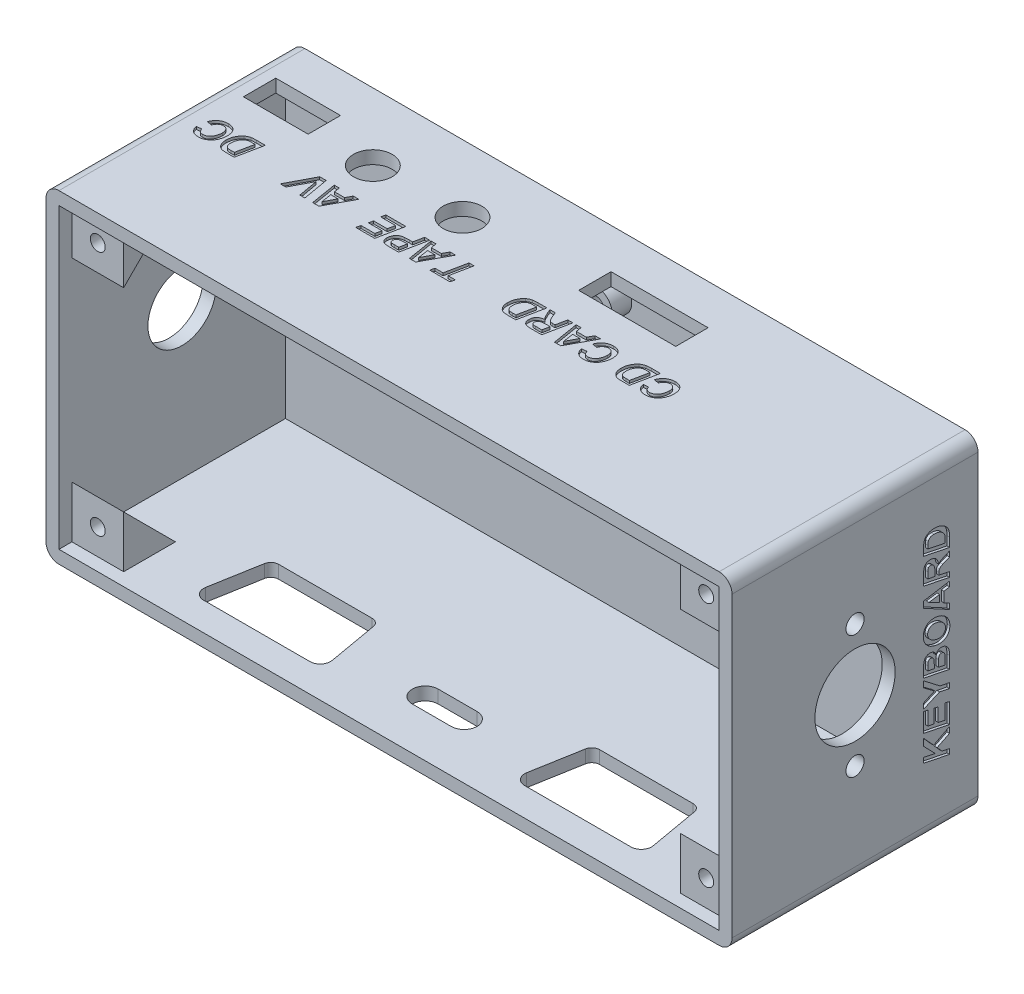
SolidWorks part; units mm, degrees
material "ABS"
ref_plane "Спереди" through (0, 0, 0) normal (0, 0, 1) x (1, 0, 0)
ref_plane "Сверху" through (0, 0, 0) normal (0, 1, 0) x (1, 0, 0)
ref_plane "Справа" through (0, 0, 0) normal (1, 0, 0) x (0, 0, -1)
sketch "Эскиз1" plane through (0, 0, 0) normal (0, 0, 1) x (1, 0, 0)
  line L1 (-53, -25) -> (53, -25)
  line L2 (-53, -25) -> (-53, 25)
  line L3 (-53, 25) -> (53, 25)
  line L4 (53, -25) -> (53, 25)
  line L5 (-53, -25) -> (53, 25) construction
  line L6 (-53, 25) -> (53, -25) construction
  point P0 (0, 0)
  dimension "D1" = 106
  dimension "D2" = 50
extrude "CaseBody" add sketch "Эскиз1" along normal blind 3
sketch "Эскиз2" plane through (0, 0, 3) normal (0, 0, 1) x (1, 0, 0)
  line L0 (53, 25) -> (-53, 25) construction
  line L1 (-51, -23) -> (51, -23)
  line L2 (-51, -23) -> (-51, 23)
  line L3 (-51, 23) -> (51, 23)
  line L4 (51, -23) -> (51, 23)
  line L5 (-51, -23) -> (51, 23) construction
  line L6 (-51, 23) -> (51, -23) construction
  line L7 (53, -25) -> (53, 25) construction
  line L9 (-53, -25) -> (53, -25)
  line L10 (-53, -25) -> (-53, 25)
  line L11 (-53, 25) -> (53, 25)
  line L12 (53, -25) -> (53, 25)
  line L13 (-53, -25) -> (53, 25) construction
  line L14 (-53, 25) -> (53, -25) construction
  point P0 (0, 0)
  point P10 (0, 0)
  dimension "D1" = 2
  dimension "D2" = 2
extrude "CaseBody2" add sketch "Эскиз2" along normal blind 35
sketch "Эскиз3" plane through (0, 0, 3) normal (0, 0, 1) x (1, 0, 0)
  line L0 (51, 23) -> (-51, 23) construction
  line L1 (-46.625, 1.53) -> (46.625, 1.53) construction
  line L2 (-46.625, 1.53) -> (-46.625, 19.18) construction
  line L3 (-46.625, 19.18) -> (46.625, 19.18) construction
  line L4 (46.625, 1.53) -> (46.625, 19.18) construction
  line L5 (-46.625, 1.53) -> (46.625, 19.18) construction
  line L6 (-46.625, 19.18) -> (46.625, 1.53) construction
  circle A0 centre (-46.625, 1.53) radius 2.5
  circle A1 centre (46.625, 1.53) radius 2.5
  circle A2 centre (0.005, 19.18) radius 2.5
  point P0 (0, 0)
  point P13 (0, 10.355)
  dimension "D4" = 5
  dimension "D1" = 93.25
  dimension "D2" = 17.65
  dimension "D3" = 46.63
  dimension "D5" = 3.82
extrude "SizifXXSFix" add sketch "Эскиз3" along normal blind 3
sketch "Эскиз4" plane through (0, 0, 6) normal (0, 0, 1) x (1, 0, 0)
  circle A0 centre (-46.625, 1.53) radius 1.2
  circle A1 centre (0.005, 19.18) radius 1.2
  circle A2 centre (46.625, 1.53) radius 1.2
  dimension "D1" = 2.4
extrude "Holes2_5" cut sketch "Эскиз4" against normal blind 5.6
sketch "Эскиз5" plane through (0, 25, 0) normal (0, 1, 0) x (1, 0, 0)
  line L1 (-49.3, -6.2) -> (-39.3, -6.2)
  line L2 (-49.3, -6.2) -> (-49.3, -11.2)
  line L3 (-49.3, -11.2) -> (-39.3, -11.2)
  line L4 (-39.3, -6.2) -> (-39.3, -11.2)
  line L5 (-49.3, -6.2) -> (-39.3, -11.2) construction
  line L6 (-49.3, -11.2) -> (-39.3, -6.2) construction
  line L7 (2.5, -6.2) -> (17.5, -6.2)
  line L8 (2.5, -6.2) -> (2.5, -11.2)
  line L9 (2.5, -11.2) -> (17.5, -11.2)
  line L10 (17.5, -6.2) -> (17.5, -11.2)
  line L11 (2.5, -6.2) -> (17.5, -11.2) construction
  line L12 (2.5, -11.2) -> (17.5, -6.2) construction
  line L13 (53, 0) -> (-53, 0) construction
  line L14 (-53, -38) -> (-53, 0) construction
  circle A0 centre (-30.1, -10.4) radius 3
  circle A1 centre (-16.25, -10.4) radius 3
  point P0 (-44.3, -8.7)
  point P9 (10, -8.7)
  dimension "D5" = 6
  dimension "D2" = 10
  dimension "D3" = 6.2
  dimension "D4" = 5
  dimension "D6" = 13.85
  dimension "D7" = 14.2
  dimension "D8" = 26.25
  dimension "D9" = 10.4
  dimension "D10" = 5
  dimension "D11" = 15
  dimension "D12" = 22.9
extrude "SizifXXS_Holes" cut sketch "Эскиз5" against normal up to next
sketch "Эскиз7" plane through (53, 0, 0) normal (1, 0, 0) x (0, 0, -1)
  line L0 (-20, 0) -> (-6.0564, 0) construction
  line L2 (0, -25) -> (0, 25) construction
  circle A0 centre (-19, 0) radius 6.2
  circle A1 centre (-19, -9.5) radius 1.4
  circle A2 centre (-19, 9.5) radius 1.4
  dimension "D1" = 12.4
  dimension "D4" = 2.8
  dimension "D2" = 19
  dimension "D3" = 19
extrude "PS2Hole" cut sketch "Эскиз7" against normal up to next
sketch "Эскиз8" plane through (51, 0, 0) normal (-1, 0, 0) x (0, 0, 1)
  line L0 (36, 23) -> (36, 15)
  line L1 (38, 23) -> (3, 23) construction
  line L2 (36, 15) -> (28, 23)
  line L3 (28, 23) -> (36, 23)
  line L4 (38, -23) -> (38, 23) construction
  dimension "D1" = 8
  dimension "D2" = 8
  dimension "D3" = 2
extrude "CaseTopFix" add sketch "Эскиз8" along normal blind 8
sketch "Эскиз9" plane through (0, 0, 36) normal (0, 0, 1) x (1, 0, 0)
  line L0 (43, 15) -> (43, 23) construction
  line L1 (43, 23) -> (51, 23) construction
  line L2 (43, 23) -> (43, 15) construction
  line L3 (43, 15) -> (51, 15) construction
  line L4 (51, 23) -> (51, 15) construction
  line L5 (43, 23) -> (51, 15) construction
  line L6 (43, 15) -> (51, 23) construction
  line L7 (43, 23) -> (51, 23) construction
  circle A0 centre (47, 19) radius 1.15
  point P0 (47, 19)
  dimension "D1" = 2.3
extrude "CaseTopHoles" cut sketch "Эскиз9" against normal up to next
mirror "CaseTopHoles1" about plane through (0, 0, 0) normal (0, 1, 0) of "CaseTopHoles", "CaseTopFix"
mirror "CaseTopHoles2" about plane through (0, 0, 0) normal (1, 0, 0) of "CaseTopHoles", "CaseTopHoles1", "CaseTopFix"
fillet "Fillet" radius 2 4 edges at (-53, 25, 19) (53, 25, 19) (53, -25, 19) (-53, -25, 19)
sketch "Эскиз10" plane through (0, 25, 0) normal (0, 1, 0) x (1, 0, 0)
  line L0 (51, 0) -> (-51, 0) construction
  line L1 (-53, -38) -> (-53, 0) construction
  text T0 "<r180>VA</r>" font "Times New Roman" height 4
  text T1 "<r180>EPAT</r>" font "Times New Roman" height 4
  text T2 "<r180>CD</r>" font "Times New Roman" height 4
  text T3 "<r180>DRAC DC</r>" font "Times New Roman" height 4
  dimension "D1" = 16
  dimension "D2" = 22.5962
  dimension "D3" = 11.2585
  dimension "D4" = 14.4528
  dimension "D5" = 21.8
extrude "InterfaceInfo" cut sketch "Эскиз10" against normal blind 0.4
sketch "Эскиз11" plane through (53, 0, 0) normal (1, 0, 0) x (0, 0, -1)
  line L0 (-4.4, -15.5) -> (-4.4, 15.5) construction
  line L1 (0, -23) -> (0, 23) construction
  text T0 "KEYBOARD" font "Arial" height 4
  point P0 (-4.4, 0)
  dimension "D1" = 4.4
  dimension "D2" = 31
extrude "PS2Info" cut sketch "Эскиз11" against normal blind 0.4
sketch "Эскиз12" plane through (0, 23, 0) normal (0, -1, 0) x (1, 0, 0)
  line L1 (-53, 0) -> (-53, 38) construction
  line L2 (-51, 0) -> (51, 0) construction
  text T0 "© Peter Ukhov 2023" font "Arial" height 6
  dimension "D1" = 16
  dimension "D2" = 14
sketch "Эскиз13" plane through (-53, 0, 0) normal (-1, 0, 0) x (0, 0, 1)
  line L1 (0, 23) -> (0, -23) construction
  circle A0 centre (19, 0) radius 5.25
  dimension "D1" = 10.5
  dimension "D2" = 19
extrude "ButtonHole" cut sketch "Эскиз13" against normal up to next
sketch "Эскиз14" plane through (-53, 0, 0) normal (-1, 0, 0) x (0, 0, 1)
  line L0 (6.2274, 10.1387) -> (6.2274, -12.1287) construction
  text T0 "POWER" font "Arial" height 4
extrude "ButtonInfo" cut sketch "Эскиз14" against normal blind 0.4
extrude "CopyLeft" cut sketch "Эскиз12" against normal blind 0.4
sketch "Эскиз15" plane through (0, -25, 0) normal (0, -1, 0) x (1, 0, 0)
  line L0 (-3, 29.4) -> (3, 29.4) construction
  line L1 (-3, 31.4) -> (3, 31.4)
  line L2 (-3, 27.4) -> (3, 27.4)
  line L3 (-51, 38) -> (51, 38) construction
  arc A0 (-3, 31.4) -> (-3, 27.4) centre (-3, 29.4) ccw
  arc A1 (3, 27.4) -> (3, 31.4) centre (3, 29.4) ccw
  point P2 (0, 29.4)
  dimension "D1" = 4
  dimension "D2" = 6
  dimension "D3" = 8.6
extrude "USBArduinoNano" cut sketch "Эскиз15" against normal up to next
sketch "Эскиз16" plane through (0, -25, 0) normal (0, -1, 0) x (1, 0, 0)
  line L0 (-34.5757, 31.755) -> (-33.2126, 24.0245)
  line L1 (-32.0308, 23.0329) -> (-17.5692, 23.0329)
  line L2 (-16.3874, 24.0245) -> (-15.0243, 31.755)
  line L3 (-16.6, 33.6329) -> (-33, 33.6329)
  line L4 (-33, 33.6329) -> (-17.5692, 23.0329) construction
  line L5 (-32.0308, 23.0329) -> (-16.6, 33.6329) construction
  line L6 (-51, 38) -> (51, 38) construction
  arc A0 (-15.0243, 31.755) -> (-16.6, 33.6329) centre (-16.6, 32.0329) ccw
  arc A1 (-33, 33.6329) -> (-34.5757, 31.755) centre (-33, 32.0329) ccw
  arc A2 (-17.5692, 23.0329) -> (-16.3874, 24.0245) centre (-17.5692, 24.2329) ccw
  arc A3 (-33.2126, 24.0245) -> (-32.0308, 23.0329) centre (-32.0308, 24.2329) ccw
  point P0 (-24.8, 28)
  dimension "D1" = 1.6
  dimension "D2" = 1.2
  dimension "D3" = 24.8
  dimension "D4" = 10
  dimension "D5" = 16.4
  dimension "D7" = 10.6
  dimension "D8" = 80
  dimension "D9" = 80
extrude "NESCut1" cut sketch "Эскиз16" against normal up to next
mirror "NESCut2" about plane through (0, 0, 0) normal (1, 0, 0) of "NESCut1"
equation "\"D1@Эскиз1\"=100+2*2+2"
equation "\"D5@Эскиз3\"=3.42+0.4"
equation "\"D2@Эскиз15\"=10-2-2"
equation "\"12ю5\"=12"
